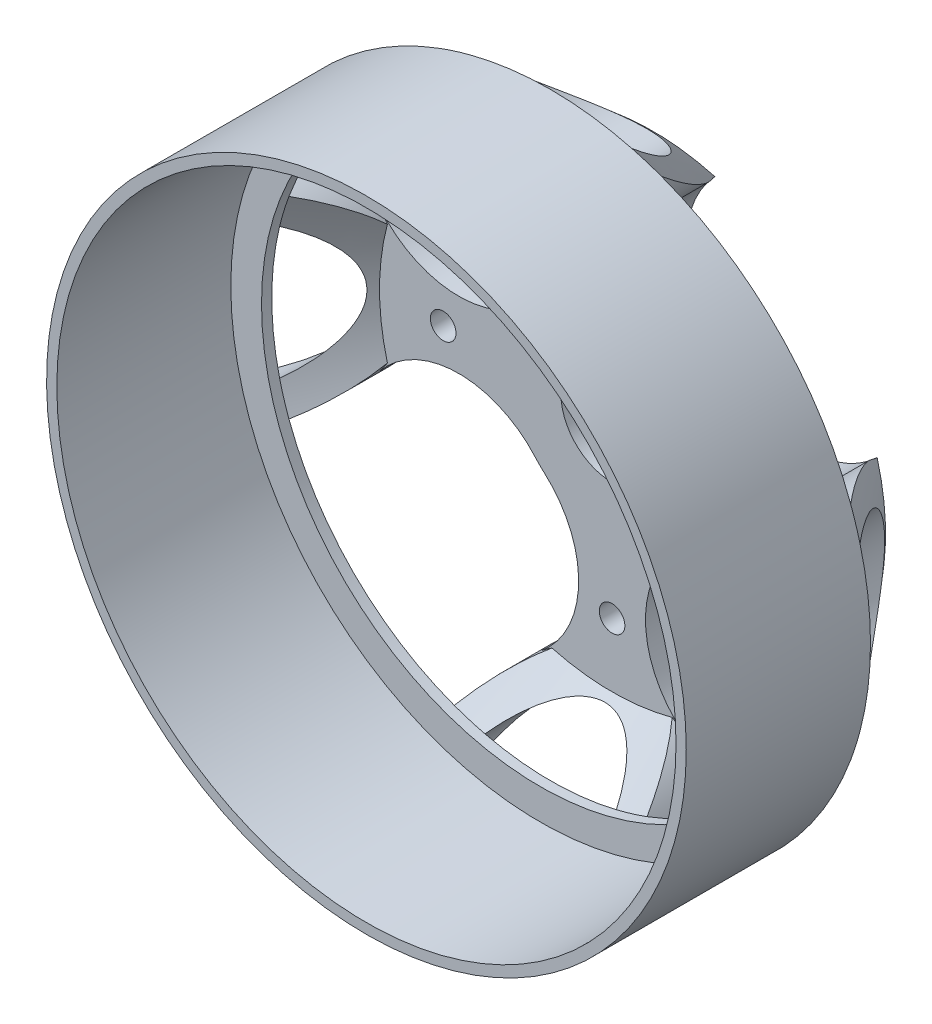
SolidWorks part; units mm, degrees
ref_plane "Front Plane" through (0, 0, 0) normal (0, 0, 1) x (1, 0, 0)
ref_plane "Top Plane" through (0, 0, 0) normal (0, 1, 0) x (1, 0, 0)
ref_plane "Right Plane" through (0, 0, 0) normal (1, 0, 0) x (0, 0, -1)
sketch "Sketch1" plane through (0, 0, 0) normal (0, 0, 1) x (1, 0, 0)
  circle A0 centre (0, 0) radius 31.25
  circle A1 centre (0, 0) radius 30.25
  dimension "D1" = 62.5
  dimension "D2" = 1
extrude "Boss-Extrude1" add sketch "Sketch1" along normal blind 17
sketch "Sketch2" plane through (0, 0, 0) normal (0, 0, -1) x (-1, 0, 0)
  circle A0 centre (0, 0) radius 27.25
  circle A1 centre (0, 0) radius 31.25
  circle A2 centre (0, 0) radius 31.25
  dimension "D1" = 0
  dimension "D2" = 4
extrude "Boss-Extrude2" add sketch "Sketch2" along normal blind 1
ref_plane "Plane1" through (0, 0, -11) normal (0, 0, -1) x (-1, 0, 0)
sketch "Sketch4" plane through (0, 0, -11) normal (0, 0, -1) x (-1, 0, 0)
  line L0 (0, 0) -> (0, 16.5) construction
  line L1 (0, 0) -> (0, -16.5) construction
  line L2 (0, 0) -> (-16.5, 0) construction
  line L3 (0, 0) -> (16.5, 0) construction
  circle A0 centre (0, 0) radius 10
  circle A1 centre (0, 0) radius 16.5 construction
  circle A3 centre (0, 0) radius 31.25 construction
  arc A4 (-29.314, 10.8283) -> (-30.226, 7.9342) centre (0, 0) ccw
  arc A6 (29.314, 10.8283) -> (29.314, -10.8283) centre (31.25, 0) ccw
  arc A7 (30.226, 7.9342) -> (30.226, -7.9342) centre (31.25, 0) ccw
  arc A8 (7.4845, 6.6319) -> (22.7219, 6.9477) centre (14.969, 13.2638) ccw
  arc A9 (7.4845, -6.6319) -> (22.7219, -6.9477) centre (14.969, -13.2638) cw
  arc A10 (6.6319, -7.4845) -> (6.9477, -22.7219) centre (13.2638, -14.969) ccw
  arc A11 (-6.6319, -7.4845) -> (-6.9477, -22.7219) centre (-13.2638, -14.969) cw
  arc A12 (10.8283, -29.314) -> (-10.8283, -29.314) centre (0, -31.25) ccw
  arc A13 (7.9342, -30.226) -> (-7.9342, -30.226) centre (0, -31.25) ccw
  arc A14 (-7.4845, -6.6319) -> (-22.7219, -6.9477) centre (-14.969, -13.2638) ccw
  arc A15 (-7.4845, 6.6319) -> (-22.7219, 6.9477) centre (-14.969, 13.2638) cw
  arc A16 (-29.314, -10.8283) -> (-29.314, 10.8283) centre (-31.25, 0) ccw
  arc A17 (-30.226, -7.9342) -> (-30.226, 7.9342) centre (-31.25, 0) ccw
  arc A18 (-6.6319, 7.4845) -> (-6.9477, 22.7219) centre (-13.2638, 14.969) ccw
  arc A19 (6.6319, 7.4845) -> (6.9477, 22.7219) centre (13.2638, 14.969) cw
  arc A20 (-10.8283, 29.314) -> (10.8283, 29.314) centre (0, 31.25) ccw
  arc A21 (-7.9342, 30.226) -> (7.9342, 30.226) centre (0, 31.25) ccw
  arc A22 (-30.226, -7.9342) -> (-29.314, -10.8283) centre (0, 0) ccw
  arc A23 (-10.8283, -29.314) -> (-7.9342, -30.226) centre (0, 0) ccw
  arc A24 (7.9342, -30.226) -> (10.8283, -29.314) centre (0, 0) ccw
  arc A25 (29.314, -10.8283) -> (30.226, -7.9342) centre (0, 0) ccw
  arc A26 (30.226, 7.9342) -> (29.314, 10.8283) centre (0, 0) ccw
  arc A27 (10.8283, 29.314) -> (7.9342, 30.226) centre (0, 0) ccw
  arc A28 (-7.9342, 30.226) -> (-10.8283, 29.314) centre (0, 0) ccw
  circle A29 centre (0, 0) radius 5
  point P46 (0, 0)
  point P57 (0, 16.5)
  point P58 (-16.5, 0)
  point P59 (0, -16.5)
  point P60 (16.5, 0)
  dimension "D1" = 20
  dimension "D2" = 33
  dimension "D3" = 16
  dimension "D4" = 22
  dimension "D5" = 10
  dimension "D7" = 10
  dimension "D6" = 4
extrude "Boss-Extrude4" add sketch "Sketch4" against normal blind 4 separate body contours A20 A18 A0 A19 | A0 A29 | A16 A14 A0 A15 | A12 A10 A0 A11 | A0 A9 A6 A8 region at (-9.0855, -3.4462, -11) region at (-15.1685, 0, -11) region at (0, 15.1685, -11) region at (0, -15.1685, -11) region at (15.1685, 0, -11)
sketch "Sketch6" plane through (0, 0, 0) normal (1, 0, 0) x (0, 0, -1)
  line L0 (0, 0) -> (19.3078, 0) construction
  line L1 (11, 20.25) -> (11, 29.314) construction
  line L2 (11, 20.25) -> (11, 22.7219)
  line L3 (11, 20.25) -> (7, 20.25)
  line L4 (7, 22.7219) -> (11, 22.7219) construction
  line L5 (7, 22.7219) -> (11, 22.7219)
  line L6 (7, 22.7219) -> (1, 27.25)
  line L7 (11, 22.7219) -> (1, 31.25)
  line L8 (1, 27.25) -> (1, 31.25)
  line L9 (7, 20.25) -> (7, 22.7219)
  line L10 (1, 31.25) -> (11, 31.25)
  line L11 (11, -2.6224) -> (11, 2.6224) construction
  line L12 (11, 31.25) -> (11, 22.7219)
  line L13 (1, 27.25) -> (1, 20.25)
  line L14 (1, -31.25) -> (1, 31.25) construction
  line L15 (1, 20.25) -> (7, 20.25)
  dimension "D1" = 13.1426
  dimension "D2" = 7.5169
  dimension "D3" = 4
  dimension "D4" = 31.25
extrude "Boss-Extrude5" add sketch "Sketch4<10>" against normal blind 10 contours A17 A22 A16 A4 | A13 A24 A12 A23 | A20 A27 A21 A28 | A6 A25 A7 A26 region at (-9.274, -25.7907, -11) region at (20.4884, 0, -11)
sketch "Sketch4<10>" plane through (0, 0, -11) normal (0, 0, -1) x (-1, 0, 0) same geometry as "Sketch4"
revolve "Cut-Revolve3" cut sketch "Sketch6" angle 360 about L0 region at (0, 28.4073, -7.6667) region at (0, 22.7984, -3.5219)
hole_wizard "M3x0.5 Tapped Hole1" positions "3DSketch1" profile "Sketch7" tap size "M3x0.5" standard "ANSI Metric" end condition through all
sketch3d "3DSketch1"
  point P0 (0, 16.5, -11)
  point P3 (16.5, 0, -11)
  point P6 (-16.5, 0, -11)
  point P9 (0, -16.5, -11)
sketch "Sketch7" plane through (0, 16.5, -11) normal (1, 0, 0) x (0, 1, 0)
  line L0 (0, 0) -> (0, 28)
  line L1 (0, 28) -> (1.25, 28)
  line L2 (1.25, 28) -> (1.25, 0)
  line L5 (1.25, 0) -> (0, 0)
  line L11 (0, -6.35) -> (0, 107.95) construction
  dimension "Thru Tap Drill Dia." = 2.5
  dimension "Thru Tap Drill Depth" = 28
cosmetic thread "Hole Thread1" parameters "D2"=3
cosmetic thread "Hole Thread2" parameters "D2"=3
cosmetic thread "Hole Thread3" parameters "D2"=3
cosmetic thread "Hole Thread4" parameters "D2"=3
